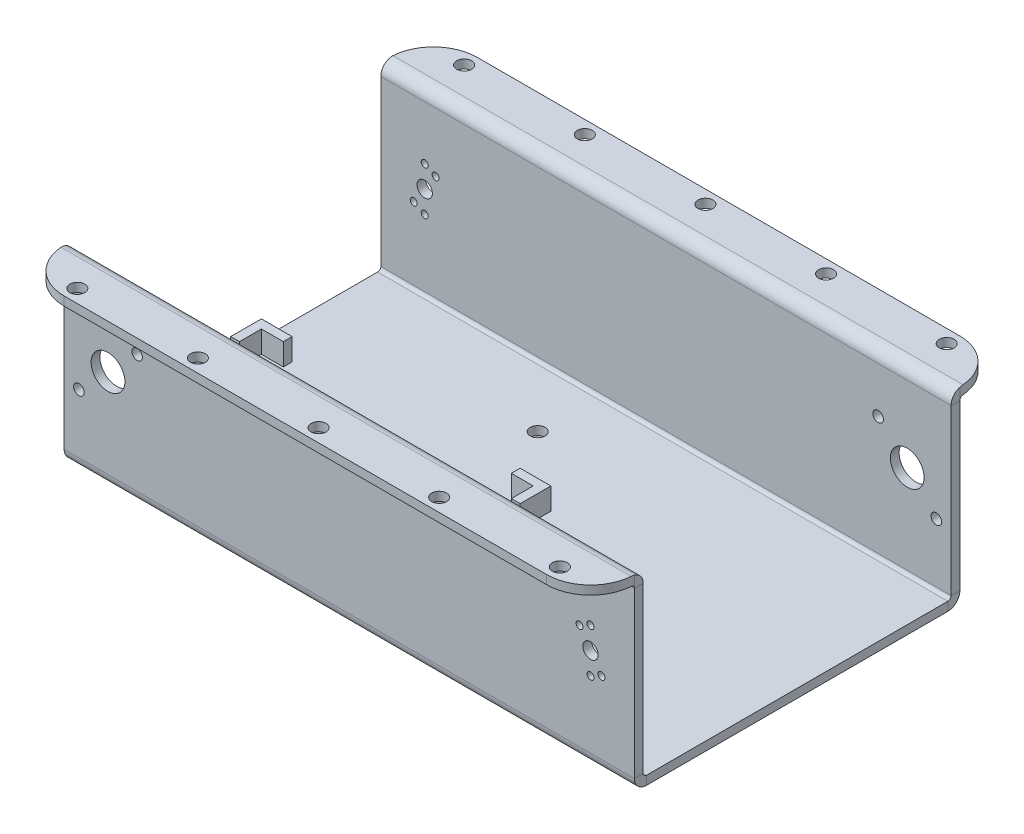
SolidWorks part; units mm, degrees
note: The reader was unsure of these and kept them because the rebuilt part matched: flange length of "边线-法兰1", "边线-法兰2".
material "PE(聚乙烯)"
ref_plane "前视基准面" through (0, 0, 0) normal (0, 0, 1) x (1, 0, 0)
ref_plane "上视基准面" through (0, 0, 0) normal (0, 1, 0) x (1, 0, 0)
ref_plane "右视基准面" through (0, 0, 0) normal (1, 0, 0) x (0, 0, -1)
other "Configuration Table"
sketch "草图1" plane through (0, 0, 0) normal (0, 1, 0) x (1, 0, 0)
  line L1 (-65, 37.1) -> (65, 37.1)
  line L2 (-65, 37.1) -> (-65, -37.1)
  line L3 (-65, -37.1) -> (65, -37.1)
  line L4 (65, 37.1) -> (65, -37.1)
  line L5 (-65, 37.1) -> (65, -37.1) construction
  line L6 (-65, -37.1) -> (65, 37.1) construction
  point P0 (0, 0)
  dimension "D1" = 130
  dimension "D2" = 74.2
base flange "基体-法兰1" sketch "草图1" thickness 2 reverse thickness direction no parameters "D1"=0.7366
edge flange "边线-法兰1" sketch "草图10" flange profiles "草图10", "草图11" flange angle 90 flange length 43 flange position material inside bend radius 0.7366 thickness 2 relief rectangular parameters "D6"=10, "D8"=1
sketch "草图10" plane through (0, 0, 37.1) normal (0, 0, 1) x (1, 0, 0)
  line L0 (-65, 0) -> (65, 0) construction
  line L1 (-65, 0) -> (65, 0)
  line L2 (-65, 0) -> (-65, 41)
  line L3 (-65, 41) -> (65, 41)
  line L4 (65, 41) -> (65, 0)
sketch "草图11" plane through (0, 0, -37.1) normal (0, 0, -1) x (-1, 0, 0)
  line L0 (-65, 0) -> (65, 0) construction
  line L1 (-65, 0) -> (65, 0)
  line L2 (-65, 0) -> (-65, 41)
  line L3 (-65, 41) -> (65, 41)
  line L4 (65, 41) -> (65, 0)
bend "边线折弯1" bend radius 0.7366 bend angle 90 parameters "D5"=1
bend "边线折弯2" bend radius 0.7366 bend angle 90 parameters "D5"=2
edge flange "边线-法兰2" sketch "草图16" flange profiles "草图16", "草图17" flange angle 90 flange length 12 flange position material inside bend radius 0.7366 thickness 2 relief rectangular parameters "D6"=10, "D8"=1
sketch "草图16" plane through (0, 41, 37.1) normal (0, 1, 0) x (-1, 0, 0)
  line L0 (-65, 0) -> (65, 0) construction
  line L1 (-65, 0) -> (65, 0)
  line L2 (-65, 0) -> (-65, 10)
  line L3 (-65, 10) -> (65, 10)
  line L4 (65, 10) -> (65, 0)
sketch "草图17" plane through (0, 41, -37.1) normal (0, 1, 0) x (1, 0, 0)
  line L0 (-65, 0) -> (65, 0) construction
  line L1 (-65, 0) -> (65, 0)
  line L2 (-65, 0) -> (-65, 10)
  line L3 (-65, 10) -> (65, 10)
  line L4 (65, 10) -> (65, 0)
bend "边线折弯3" bend radius 0.7366 bend angle 90 parameters "D5"=3
bend "边线折弯4" bend radius 0.7366 bend angle 90 parameters "D5"=4
sketch "草图24" plane through (0, 0, -37.1) normal (0, 0, -1) x (-1, 0, 0)
  line L0 (57.3827, 5.414) -> (62.1487, 5.414) construction
  line L1 (62.1487, 5.414) -> (62.1487, 5.819) construction
  line L2 (62.1487, 5.819) -> (57.3827, 5.819) construction
  line L3 (57.3827, 5.819) -> (57.3827, 5.414) construction
  line L4 (57.3827, 5.414) -> (62.1487, 5.414) construction
  line L5 (62.1487, 5.414) -> (62.1487, 5.819) construction
  line L6 (62.1487, 5.819) -> (57.3827, 5.819) construction
  line L7 (57.3827, 5.819) -> (57.3827, 5.414) construction
  line L8 (57.3827, 5.6165) -> (62.1487, 5.6165) construction
  line L9 (59.7657, 5.819) -> (59.7657, 5.414) construction
  arc A1 (53.882, 22) -> (56.118, 22) centre (55, 21) ccw construction
  circle A2 centre (55, 16) radius 0.625 construction
  circle A3 centre (57.5, 17.25) radius 0.8 construction
  circle A4 centre (52.5, 24.75) radius 0.8 construction
  circle A5 centre (55, 26) radius 0.625 construction
  circle A6 centre (-55, 21) radius 2 construction
  arc A7 (53.882, 22) -> (56.118, 22) centre (55, 21) ccw construction
  circle A8 centre (55, 16) radius 0.625 construction
  circle A9 centre (57.5, 17.25) radius 0.8 construction
  circle A10 centre (52.5, 24.75) radius 0.8 construction
  circle A11 centre (55, 26) radius 0.625 construction
  circle A12 centre (59.7657, 5.6165) radius 1
  circle A18 centre (62.2657, 5.6165) radius 1
  circle A37 centre (41.0157, 3.4515) radius 1
  circle A38 centre (28.5157, 20.772) radius 1
  circle A39 centre (37.2657, 40.2575) radius 1
  circle A40 centre (58.5157, 42.4226) radius 1
  circle A41 centre (71.0157, 25.1021) radius 1
  point P29 (59.7657, 5.6165)
  point P40 (39.7657, 5.6165)
  point P41 (39.7657, 5.6165)
  point P46 (49.7657, 22.937)
  point P65 (39.7657, 5.6165)
  dimension "D1" = 2
  dimension "D3" = 2
  dimension "D2" = 2.5
  dimension "D4" = 6
sketch "草图25" plane through (0, 0, 37.1) normal (0, 0, 1) x (1, 0, 0)
  arc A1 (53.882, 22) -> (56.118, 22) centre (55, 21) ccw construction
  circle A2 centre (55, 16) radius 0.625 construction
  circle A3 centre (57.5, 17.25) radius 0.8 construction
  circle A4 centre (52.5, 24.75) radius 0.8 construction
  circle A5 centre (55, 26) radius 0.625 construction
  circle A6 centre (-55, 21) radius 2
  arc A7 (53.882, 22) -> (56.118, 22) centre (55, 21) ccw
  circle A8 centre (55, 16) radius 0.625
  circle A9 centre (57.5, 17.25) radius 0.8
  circle A10 centre (52.5, 24.75) radius 0.8
  circle A11 centre (55, 26) radius 0.625
hole_wizard "M1.4 间隙孔1" positions "草图27" profile "草图28" hole size "M1.4" standard "GB" end condition up to next
sketch "草图27" plane through (0, 0, -37.1) normal (0, 0, -1) x (-1, 0, 0)
  point P0 (52.5, 24.75)
  point P3 (55, 26)
  point P6 (57.5, 17.25)
  point P9 (55, 16)
sketch "草图28" plane through (-52.5, 24.75, -37.1) normal (1, 0, 0) x (0, 1, 0)
  line L0 (0, 0) -> (0, 2)
  line L1 (0, 2) -> (0.8, 2)
  line L2 (0.8, 2) -> (0.8, 0)
  line L5 (0.8, 0) -> (0, 0)
  line L11 (0, -6.35) -> (0, 107.95) construction
  dimension "通孔孔直径" = 1.6
  dimension "通孔孔深度" = 2
hole_wizard "M1.4 间隙孔2" positions "草图29" profile "草图30" hole size "M1.4" standard "GB" end condition up to next
sketch "草图29" plane through (0, 0, 37.1) normal (0, 0, 1) x (1, 0, 0)
  point P0 (52.5, 24.75)
  point P3 (55, 26)
  point P6 (57.5, 17.25)
  point P9 (55, 16)
sketch "草图30" plane through (52.5, 24.75, 37.1) normal (1, 0, 0) x (0, -1, 0)
  line L0 (0, 0) -> (0, 2)
  line L1 (0, 2) -> (0.8, 2)
  line L2 (0.8, 2) -> (0.8, 0)
  line L5 (0.8, 0) -> (0, 0)
  line L11 (0, -6.35) -> (0, 107.95) construction
  dimension "通孔孔直径" = 1.6
  dimension "通孔孔深度" = 2
hole_wizard "Ø3.5 (3.5) 直径孔1" positions "草图31" profile "草图32" hole size "Ø3.5" standard "GB" end condition up to next
sketch "草图31" plane through (0, 0, -37.1) normal (0, 0, -1) x (-1, 0, 0)
  point P0 (55, 21)
sketch "草图32" plane through (-55, 21, -37.1) normal (1, 0, 0) x (0, 1, 0)
  line L0 (0, 0) -> (0, 2)
  line L1 (0, 2) -> (1.75, 2)
  line L2 (1.75, 2) -> (1.75, 0)
  line L5 (1.75, 0) -> (0, 0)
  line L11 (0, -6.35) -> (0, 107.95) construction
  dimension "通孔孔直径" = 3.5
  dimension "通孔孔深度" = 2
hole_wizard "Ø3.5 (3.5) 直径孔2" positions "草图33" profile "草图34" hole size "Ø3.5" standard "GB" end condition up to next
sketch "草图33" plane through (0, 0, 37.1) normal (0, 0, 1) x (1, 0, 0)
  point P0 (55, 21)
sketch "草图34" plane through (55, 21, 37.1) normal (1, 0, 0) x (0, -1, 0)
  line L0 (0, 0) -> (0, 2)
  line L1 (0, 2) -> (1.75, 2)
  line L2 (1.75, 2) -> (1.75, 0)
  line L5 (1.75, 0) -> (0, 0)
  line L11 (0, -6.35) -> (0, 107.95) construction
  dimension "通孔孔直径" = 3.5
  dimension "通孔孔深度" = 2
hole_wizard "Ø7.7 (7.7) 直径孔1" positions "草图35" profile "草图36" hole size "Ø7.7" standard "GB" end condition up to next
sketch "草图35" plane through (0, 0, -37.1) normal (0, 0, -1) x (-1, 0, 0)
  point P0 (-55, 21)
sketch "草图36" plane through (55, 21, -37.1) normal (1, 0, 0) x (0, 1, 0)
  line L0 (0, 0) -> (0, 2)
  line L1 (0, 2) -> (3.85, 2)
  line L2 (3.85, 2) -> (3.85, 0)
  line L5 (3.85, 0) -> (0, 0)
  line L11 (0, -6.35) -> (0, 107.95) construction
  dimension "通孔孔直径" = 7.7
  dimension "通孔孔深度" = 2
hole_wizard "Ø7.7 (7.7) 直径孔2" positions "草图37" profile "草图38" hole size "Ø7.7" standard "GB" end condition up to next
sketch "草图37" plane through (0, 0, 37.1) normal (0, 0, 1) x (1, 0, 0)
  point P0 (-55, 21)
sketch "草图38" plane through (-55, 21, 37.1) normal (1, 0, 0) x (0, -1, 0)
  line L0 (0, 0) -> (0, 2)
  line L1 (0, 2) -> (3.85, 2)
  line L2 (3.85, 2) -> (3.85, 0)
  line L5 (3.85, 0) -> (0, 0)
  line L11 (0, -6.35) -> (0, 107.95) construction
  dimension "通孔孔直径" = 7.7
  dimension "通孔孔深度" = 2
sketch "草图43" plane through (0, 41, 0) normal (0, 1, 0) x (1, 0, 0)
  line L0 (65, 47.1) -> (-65, 47.1) construction
  line L1 (-55, -44.1) -> (55, -44.1) construction
  line L2 (-55, -44.1) -> (-55, 44.1) construction
  line L3 (-55, 44.1) -> (55, 44.1) construction
  line L4 (55, -44.1) -> (55, 44.1) construction
  line L5 (-55, -44.1) -> (55, 44.1) construction
  line L6 (-55, 44.1) -> (55, -44.1) construction
  line L8 (65, 37.8366) -> (65, 47.1) construction
  line L9 (0, 44.1) -> (0, -44.1) construction
  line L10 (-27.5, 44.1) -> (-27.5, -44.1) construction
  line L11 (27.5, 44.1) -> (27.5, -44.1) construction
  point P0 (0, 0)
  dimension "D1" = 3
  dimension "D2" = 10
  dimension "D3" = 27.5
hole_wizard "M3 间隙孔2" positions "草图44" profile "草图45" hole size "M3" standard "GB" end condition through all
sketch "草图44" plane through (0, 41, 0) normal (0, 1, 0) x (1, 0, 0)
  line L0 (-55, 44.1) -> (55, 44.1) construction
  point P0 (-55, 44.1)
  point P3 (-27.5, 44.1)
  point P6 (27.5, 44.1)
  point P9 (55, 44.1)
  point P12 (55, -44.1)
  point P15 (27.5, -44.1)
  point P18 (0, -44.1)
  point P21 (-27.5, -44.1)
  point P24 (-55, -44.1)
  point P27 (0, 44.1)
sketch "草图45" plane through (-55, 41, -44.1) normal (1, 0, 0) x (0, 0, 1)
  line L0 (0, 0) -> (0, 43)
  line L1 (0, 43) -> (1.7, 43)
  line L2 (1.7, 43) -> (1.7, 0)
  line L5 (1.7, 0) -> (0, 0)
  line L11 (0, -6.35) -> (0, 107.95) construction
  dimension "通孔孔直径" = 3.4
  dimension "通孔孔深度" = 43
sketch "草图46" plane through (0, 0, 0) normal (0, 1, 0) x (1, 0, 0)
  line L2 (1.9747, 6.87) -> (-5.0253, 6.87)
  line L3 (-64, 6.87) -> (-64, -0.13)
  line L17 (-0.0253, -32.8747) -> (-0.0253, 7.1) construction
  line L18 (-0.0253, 4.87) -> (-62, 4.87) construction
  line L19 (-62, 7.1) -> (-62, -32.8747) construction
  line L24 (-57, 6.87) -> (-57, 4.87)
  line L25 (-64, -0.13) -> (-62, -0.13)
  line L27 (-5.0253, 6.87) -> (-5.0253, 4.87)
  line L28 (-62, 4.87) -> (-57, 4.87)
  line L29 (-62, 4.87) -> (-62, -0.13)
  line L31 (-0.0253, -0.13) -> (1.9747, -0.13)
  line L36 (-0.0253, 4.87) -> (-0.0253, -0.13)
  line L37 (-0.0253, 4.87) -> (-5.0253, 4.87)
  line L40 (-57, 6.87) -> (-64, 6.87)
  line L43 (1.9747, -0.13) -> (1.9747, 6.87)
  dimension "D3" = 5
  dimension "D4" = 5
  dimension "D6" = 5
extrude "凸台-拉伸1" add sketch "草图46" along normal blind 5
sketch "草图67" plane through (0, 0, 35.1) normal (0, 0, -1) x (-1, 0, 0)
  circle A4 centre (48.3667, 27.8007) radius 1.2
  circle A5 centre (61.6333, 14.1993) radius 1.2
  circle A6 centre (-48.3667, 27.8007) radius 1.2
  circle A7 centre (-61.6333, 14.1993) radius 1.2
hole_wizard "M2 间隙孔4" positions "草图70" profile "草图71" hole size "M2" standard "GB" end condition up to next
sketch "草图70" plane through (0, 0, -37.1) normal (0, 0, -1) x (-1, 0, 0)
  point P0 (-48.3667, 27.8007)
  point P3 (-61.6333, 14.1993)
sketch "草图71" plane through (48.3667, 27.8007, -37.1) normal (1, 0, 0) x (0, 1, 0)
  line L0 (0, 0) -> (0, 2)
  line L1 (0, 2) -> (1.2, 2)
  line L2 (1.2, 2) -> (1.2, 0)
  line L5 (1.2, 0) -> (0, 0)
  line L11 (0, -6.35) -> (0, 107.95) construction
  dimension "通孔孔直径" = 2.4
  dimension "通孔孔深度" = 2
hole_wizard "M2 间隙孔5" positions "草图72" profile "草图73" hole size "M2" standard "GB" end condition up to next
sketch "草图72" plane through (0, 0, 35.1) normal (0, 0, -1) x (-1, 0, 0)
  point P0 (48.3667, 27.8007)
  point P3 (61.6333, 14.1993)
sketch "草图73" plane through (-48.3667, 27.8007, 35.1) normal (1, 0, 0) x (0, 1, 0)
  line L0 (0, 0) -> (0, 2)
  line L1 (0, 2) -> (1.2, 2)
  line L2 (1.2, 2) -> (1.2, 0)
  line L5 (1.2, 0) -> (0, 0)
  line L11 (0, -6.35) -> (0, 107.95) construction
  dimension "通孔孔直径" = 2.4
  dimension "通孔孔深度" = 2
hole_wizard "M3 间隙孔3" positions "草图74" profile "草图75" hole size "M3" standard "GB"
sketch "草图74" plane through (0, 0, 0) normal (0, 1, 0) x (1, 0, 0)
  line L0 (65, 35.1) -> (-65, 35.1) construction
  line L1 (-65, 34.3634) -> (-65, -34.3634) construction
  point P0 (-15.23, 21.09)
  dimension "D1" = 14.01
  dimension "D2" = 49.77
sketch "草图75" plane through (-15.23, 0, -21.09) normal (1, 0, 0) x (0, 0, 1)
  line L0 (0, 0) -> (0, 3)
  line L1 (0, 3) -> (1.7, 1.9785)
  line L2 (1.7, 1.9785) -> (1.7, 0)
  line L5 (1.7, 0) -> (0, 0)
  line L10 (0, 3) -> (-1.7, 1.9785) construction
  line L11 (0, -6.35) -> (0, 107.95) construction
  dimension "孔直径" = 3.4
  dimension "孔深度" = 3
  dimension "导头角度" = 118
fillet "圆角1" radius 10 4 edges at (65, 40, -47.1) (65, 40, 47.1) (-65, 40, 47.1) (-65, 40, -47.1)
sketch "草图78" plane through (0, 41, 0) normal (0, 1, 0) x (1, 0, 0)
  line L0 (-55, -47.1) -> (55, -47.1) construction
  arc A0 (-64.9728, -37.8366) -> (-52.5452, -47.1) centre (-51.6691, -32.9566) ccw
sketch "折弯-线1" [suppressed] plane through (0, 0, 0) normal (0, 1, 0) x (1, 0, 0)
sketch "边界框1" [suppressed] plane through (0, 0, 0) normal (0, 1, 0) x (1, 0, 0)
sheet metal parameters "钣金6" thickness 2 parameters "D1"=0.7366
flat pattern "平板型式6" [suppressed]
sketch "折弯-线2" plane through (0, 0, 0) normal (0, 1, 0) x (1, 0, 0)
sketch "边界框2" [suppressed] plane through (0, 0, 0) normal (0, 1, 0) x (1, 0, 0)
sheet metal parameters "钣金7" thickness 2 parameters "D1"=0.7366
flat pattern "平板型式6" [suppressed]
sketch "折弯-线2" plane through (0, 0, 0) normal (0, 1, 0) x (1, 0, 0)
sketch "边界框2" [suppressed] plane through (0, 0, 0) normal (0, 1, 0) x (1, 0, 0)
bend of the flat pattern "展平-<边线折弯1>1"
bend of the flat pattern "展平-<边线折弯2>1"
sheet metal parameters "钣金8" thickness 2 parameters "D1"=0.7366
flat pattern "平板型式6" [suppressed]
sketch "折弯-线2" plane through (0, 0, 0) normal (0, 1, 0) x (1, 0, 0)
sketch "边界框2" [suppressed] plane through (0, 0, 0) normal (0, 1, 0) x (1, 0, 0)
bend of the flat pattern "展平-<边线折弯1>1"
bend of the flat pattern "展平-<边线折弯2>1"
bend of the flat pattern "展平-<边线折弯3>1"
bend of the flat pattern "展平-<边线折弯4>1"
sheet metal parameters "钣金12" thickness 2 parameters "D1"=0.7366
flat pattern "平板型式6" [suppressed]
sketch "折弯-线2" plane through (0, 0, 0) normal (0, 1, 0) x (1, 0, 0)
sketch "边界框2" [suppressed] plane through (0, 0, 0) normal (0, 1, 0) x (1, 0, 0)
bend of the flat pattern "展平-<边线折弯1>1"
bend of the flat pattern "展平-<边线折弯2>1"
bend of the flat pattern "展平-<边线折弯3>1"
bend of the flat pattern "展平-<边线折弯4>1"
sheet metal parameters "钣金13" thickness 2 parameters "D1"=0.7366
flat pattern "平板型式6" [suppressed]
sketch "折弯-线2" plane through (0, 0, 0) normal (0, 1, 0) x (1, 0, 0)
sketch "边界框2" [suppressed] plane through (0, 0, 0) normal (0, 1, 0) x (1, 0, 0)
bend of the flat pattern "展平-<边线折弯1>1"
bend of the flat pattern "展平-<边线折弯2>1"
bend of the flat pattern "展平-<边线折弯3>1"
bend of the flat pattern "展平-<边线折弯4>1"
sheet metal parameters "钣金14" thickness 2 parameters "D1"=0.7366
flat pattern "平板型式6" [suppressed]
sketch "折弯-线2" plane through (0, 0, 0) normal (0, 1, 0) x (1, 0, 0)
sketch "边界框2" [suppressed] plane through (0, 0, 0) normal (0, 1, 0) x (1, 0, 0)
bend of the flat pattern "展平-<边线折弯1>1"
bend of the flat pattern "展平-<边线折弯2>1"
bend of the flat pattern "展平-<边线折弯3>1"
bend of the flat pattern "展平-<边线折弯4>1"
sheet metal parameters "钣金15" thickness 2 parameters "D1"=0.7366
flat pattern "平板型式6" [suppressed]
sketch "折弯-线2" plane through (0, 0, 0) normal (0, 1, 0) x (1, 0, 0)
sketch "边界框2" [suppressed] plane through (0, 0, 0) normal (0, 1, 0) x (1, 0, 0)
bend of the flat pattern "展平-<边线折弯1>1"
bend of the flat pattern "展平-<边线折弯2>1"
bend of the flat pattern "展平-<边线折弯3>1"
bend of the flat pattern "展平-<边线折弯4>1"
sheet metal parameters "钣金16" thickness 2 parameters "D1"=0.7366
flat pattern "平板型式6" [suppressed]
sketch "折弯-线2" plane through (0, 0, 0) normal (0, 1, 0) x (1, 0, 0)
sketch "边界框2" [suppressed] plane through (0, 0, 0) normal (0, 1, 0) x (1, 0, 0)
bend of the flat pattern "展平-<边线折弯1>1"
bend of the flat pattern "展平-<边线折弯2>1"
bend of the flat pattern "展平-<边线折弯3>1"
bend of the flat pattern "展平-<边线折弯4>1"
sheet metal parameters "钣金17" thickness 2 parameters "D1"=0.7366
flat pattern "平板型式6" [suppressed]
sketch "折弯-线2" plane through (0, 0, 0) normal (0, 1, 0) x (1, 0, 0)
sketch "边界框2" [suppressed] plane through (0, 0, 0) normal (0, 1, 0) x (1, 0, 0)
bend of the flat pattern "展平-<边线折弯1>1"
bend of the flat pattern "展平-<边线折弯2>1"
bend of the flat pattern "展平-<边线折弯3>1"
bend of the flat pattern "展平-<边线折弯4>1"
sheet metal parameters "钣金21" thickness 2 parameters "D1"=0.7366
flat pattern "平板型式6" [suppressed]
sketch "折弯-线2" plane through (0, 0, 0) normal (0, 1, 0) x (1, 0, 0)
  line L0 (65, 72.982) -> (-65, 72.982) construction
  line L1 (-65, -72.982) -> (65, -72.982) construction
  line L2 (65, 35.7273) -> (-65, 35.7273) construction
  line L3 (-65, -35.7273) -> (65, -35.7273) construction
  line L4 (65, 72.982) -> (-65, 72.982) construction
  line L5 (-65, -72.982) -> (65, -72.982) construction
  line L6 (65, 35.7273) -> (-65, 35.7273) construction
  line L7 (-65, -35.7273) -> (65, -35.7273) construction
sketch3d "边界框2" [suppressed]
  line L0 (65, 83.6093, 0) -> (65, -83.6093, 0) construction
  line L1 (-65, 83.6093, 0) -> (-65, -83.6093, 0) construction
  line L2 (65, 83.6093, 0) -> (-65, 83.6093, 0) construction
  line L3 (65, -83.6093, 0) -> (-65, -83.6093, 0) construction
bend of the flat pattern "展平-<边线折弯1>1"
bend of the flat pattern "展平-<边线折弯2>1"
bend of the flat pattern "展平-<边线折弯3>1"
bend of the flat pattern "展平-<边线折弯4>1"
sketch "草图25-1" plane through (0, -2, 36.3546) normal (0, -1, 0) x (1, 0, 0)
  circle A6 centre (-55, 21) radius 2
  arc A7 (53.882, 22) -> (56.118, 22) centre (55, 21) ccw
  circle A8 centre (55, 16) radius 0.625
  circle A9 centre (57.5, 17.25) radius 0.8
  circle A10 centre (52.5, 24.75) radius 0.8
  circle A11 centre (55, 26) radius 0.625
sketch "草图26-1" plane through (0, -2, 36.3546) normal (0, -1, 0) x (1, 0, 0)
  circle A3 centre (35, 23.5) radius 1.45
  circle A4 centre (0, 23.5) radius 1.45
  circle A5 centre (-35, 23.5) radius 1.45
sketch "草图43-1" plane through (0, 0, -36.5093) normal (0, 1, 0) x (1, 0, 0)
  line L0 (62, 47.1) -> (-62, 47.1) construction
  line L1 (-55, -44.1) -> (55, -44.1) construction
  line L2 (-55, -44.1) -> (-55, 44.1) construction
  line L3 (-55, 44.1) -> (55, 44.1) construction
  line L4 (55, -44.1) -> (55, 44.1) construction
  line L5 (-55, -44.1) -> (55, 44.1) construction
  line L6 (-55, 44.1) -> (55, -44.1) construction
  line L8 (65, -117.1186) -> (65, 44.1) construction
  line L9 (0, 44.1) -> (0, -44.1) construction
  line L10 (-27.5, 44.1) -> (-27.5, -44.1) construction
  line L11 (27.5, 44.1) -> (27.5, -44.1) construction
  point P0 (0, 0)
  dimension "D1" = 3
  dimension "D2" = 10
  dimension "D3" = 27.5
sheet metal parameters "钣金22" thickness 2 parameters "D1"=0.7366
flat pattern "平板型式6" [suppressed]
sketch "折弯-线2" plane through (0, 0, 0) normal (0, 1, 0) x (1, 0, 0)
  line L0 (65, 72.982) -> (-65, 72.982) construction
  line L1 (-65, -72.982) -> (65, -72.982) construction
  line L2 (65, 35.7273) -> (-65, 35.7273) construction
  line L3 (-65, -35.7273) -> (65, -35.7273) construction
  line L4 (65, 72.982) -> (-65, 72.982) construction
  line L5 (-65, -72.982) -> (65, -72.982) construction
  line L6 (65, 35.7273) -> (-65, 35.7273) construction
  line L7 (-65, -35.7273) -> (65, -35.7273) construction
sketch3d "边界框2" [suppressed]
  line L0 (65, 83.6093, 0) -> (65, -83.6093, 0) construction
  line L1 (-65, 83.6093, 0) -> (-65, -83.6093, 0) construction
  line L2 (65, 83.6093, 0) -> (-65, 83.6093, 0) construction
  line L3 (65, -83.6093, 0) -> (-65, -83.6093, 0) construction
bend of the flat pattern "展平-<边线折弯1>1"
bend of the flat pattern "展平-<边线折弯2>1"
bend of the flat pattern "展平-<边线折弯3>1"
bend of the flat pattern "展平-<边线折弯4>1"
sketch "草图25-1" plane through (0, -2, 36.3546) normal (0, -1, 0) x (1, 0, 0)
  circle A6 centre (-55, 21) radius 2
  arc A7 (53.882, 22) -> (56.118, 22) centre (55, 21) ccw
  circle A8 centre (55, 16) radius 0.625
  circle A9 centre (57.5, 17.25) radius 0.8
  circle A10 centre (52.5, 24.75) radius 0.8
  circle A11 centre (55, 26) radius 0.625
sketch "草图26-1" plane through (0, -2, 36.3546) normal (0, -1, 0) x (1, 0, 0)
  circle A3 centre (35, 23.5) radius 1.45
  circle A4 centre (0, 23.5) radius 1.45
  circle A5 centre (-35, 23.5) radius 1.45
sketch "草图43-1" plane through (0, 0, -36.5093) normal (0, 1, 0) x (1, 0, 0)
  line L0 (62, 47.1) -> (-62, 47.1)
  line L1 (-55, -44.1) -> (55, -44.1) construction
  line L2 (-55, -44.1) -> (-55, 44.1) construction
  line L3 (-55, 44.1) -> (55, 44.1) construction
  line L4 (55, -44.1) -> (55, 44.1) construction
  line L5 (-55, -44.1) -> (55, 44.1) construction
  line L6 (-55, 44.1) -> (55, -44.1) construction
  line L8 (65, -117.1186) -> (65, 44.1)
  line L9 (0, 44.1) -> (0, -44.1) construction
  line L10 (-27.5, 44.1) -> (-27.5, -44.1) construction
  line L11 (27.5, 44.1) -> (27.5, -44.1) construction
  point P0 (0, 0)
  dimension "D1" = 3
  dimension "D2" = 10
  dimension "D3" = 27.5
sheet metal parameters "钣金31" thickness 2 parameters "D1"=0.7366
flat pattern "平板型式6" [suppressed]
sketch "折弯-线2" plane through (0, 0, 0) normal (0, 1, 0) x (1, 0, 0)
  line L0 (65, 72.982) -> (-65, 72.982) construction
  line L1 (-65, -72.982) -> (65, -72.982) construction
  line L2 (65, 35.7273) -> (-65, 35.7273) construction
  line L3 (-65, -35.7273) -> (65, -35.7273) construction
  line L4 (65, 72.982) -> (-65, 72.982) construction
  line L5 (-65, -72.982) -> (65, -72.982) construction
  line L6 (65, 35.7273) -> (-65, 35.7273) construction
  line L7 (-65, -35.7273) -> (65, -35.7273) construction
sketch3d "边界框2" [suppressed]
  line L0 (65, 83.6093, 0) -> (65, -83.6093, 0) construction
  line L1 (-65, 83.6093, 0) -> (-65, -83.6093, 0) construction
  line L2 (65, 83.6093, 0) -> (-65, 83.6093, 0) construction
  line L3 (65, -83.6093, 0) -> (-65, -83.6093, 0) construction
bend of the flat pattern "展平-<边线折弯1>1"
bend of the flat pattern "展平-<边线折弯2>1"
bend of the flat pattern "展平-<边线折弯3>1"
bend of the flat pattern "展平-<边线折弯4>1"
sketch "草图25-1" plane through (0, -2, 36.3546) normal (0, -1, 0) x (1, 0, 0)
  circle A6 centre (-55, 21) radius 2
  arc A7 (53.882, 22) -> (56.118, 22) centre (55, 21) ccw
  circle A8 centre (55, 16) radius 0.625
  circle A9 centre (57.5, 17.25) radius 0.8
  circle A10 centre (52.5, 24.75) radius 0.8
  circle A11 centre (55, 26) radius 0.625
sketch "草图26-1" plane through (0, -2, 36.3546) normal (0, -1, 0) x (1, 0, 0)
  circle A3 centre (35, 23.5) radius 1.45
  circle A4 centre (0, 23.5) radius 1.45
  circle A5 centre (-35, 23.5) radius 1.45
sketch "草图43-1" plane through (0, 0, -36.5093) normal (0, 1, 0) x (1, 0, 0)
  line L0 (62, 47.1) -> (-62, 47.1)
  line L1 (-55, -44.1) -> (55, -44.1) construction
  line L2 (-55, -44.1) -> (-55, 44.1) construction
  line L3 (-55, 44.1) -> (55, 44.1) construction
  line L4 (55, -44.1) -> (55, 44.1) construction
  line L5 (-55, -44.1) -> (55, 44.1) construction
  line L6 (-55, 44.1) -> (55, -44.1) construction
  line L8 (65, -117.1186) -> (65, 44.1)
  line L9 (0, 44.1) -> (0, -44.1) construction
  line L10 (-27.5, 44.1) -> (-27.5, -44.1) construction
  line L11 (27.5, 44.1) -> (27.5, -44.1) construction
  point P0 (0, 0)
  dimension "D1" = 3
  dimension "D2" = 10
  dimension "D3" = 27.5
sheet metal parameters "钣金32" thickness 2 parameters "D1"=0.7366
flat pattern "平板型式6" [suppressed]
sketch "折弯-线2" plane through (0, 0, 0) normal (0, 1, 0) x (1, 0, 0)
  line L0 (65, 72.982) -> (-65, 72.982) construction
  line L1 (-65, -72.982) -> (65, -72.982) construction
  line L2 (65, 35.7273) -> (-65, 35.7273) construction
  line L3 (-65, -35.7273) -> (65, -35.7273) construction
  line L4 (65, 72.982) -> (-65, 72.982) construction
  line L5 (-65, -72.982) -> (65, -72.982) construction
  line L6 (65, 35.7273) -> (-65, 35.7273) construction
  line L7 (-65, -35.7273) -> (65, -35.7273) construction
sketch3d "边界框2" [suppressed]
  line L0 (65, 83.6093, 0) -> (65, -83.6093, 0) construction
  line L1 (-65, 83.6093, 0) -> (-65, -83.6093, 0) construction
  line L2 (65, 83.6093, 0) -> (-65, 83.6093, 0) construction
  line L3 (65, -83.6093, 0) -> (-65, -83.6093, 0) construction
bend of the flat pattern "展平-<边线折弯1>1"
bend of the flat pattern "展平-<边线折弯2>1"
bend of the flat pattern "展平-<边线折弯3>1"
bend of the flat pattern "展平-<边线折弯4>1"
sketch "草图25-1" plane through (0, -2, 36.3546) normal (0, -1, 0) x (1, 0, 0)
  circle A6 centre (-55, 21) radius 2
  arc A7 (53.882, 22) -> (56.118, 22) centre (55, 21) ccw
  circle A8 centre (55, 16) radius 0.625
  circle A9 centre (57.5, 17.25) radius 0.8
  circle A10 centre (52.5, 24.75) radius 0.8
  circle A11 centre (55, 26) radius 0.625
sketch "草图26-1" plane through (0, -2, 36.3546) normal (0, -1, 0) x (1, 0, 0)
  circle A3 centre (35, 23.5) radius 1.45
  circle A4 centre (0, 23.5) radius 1.45
  circle A5 centre (-35, 23.5) radius 1.45
sketch "草图43-1" plane through (0, 0, -36.5093) normal (0, 1, 0) x (1, 0, 0)
  line L0 (62, 47.1) -> (-62, 47.1)
  line L1 (-55, -44.1) -> (55, -44.1) construction
  line L2 (-55, -44.1) -> (-55, 44.1) construction
  line L3 (-55, 44.1) -> (55, 44.1) construction
  line L4 (55, -44.1) -> (55, 44.1) construction
  line L5 (-55, -44.1) -> (55, 44.1) construction
  line L6 (-55, 44.1) -> (55, -44.1) construction
  line L8 (65, -117.1186) -> (65, 44.1)
  line L9 (0, 44.1) -> (0, -44.1) construction
  line L10 (-27.5, 44.1) -> (-27.5, -44.1) construction
  line L11 (27.5, 44.1) -> (27.5, -44.1) construction
  point P0 (0, 0)
  dimension "D1" = 3
  dimension "D2" = 10
  dimension "D3" = 27.5
sheet metal parameters "钣金33" thickness 2 parameters "D1"=0.7366
flat pattern "平板型式6" [suppressed]
sketch "折弯-线2" plane through (0, 0, 0) normal (0, 1, 0) x (1, 0, 0)
  line L0 (65, 72.982) -> (-65, 72.982) construction
  line L1 (-65, -72.982) -> (65, -72.982) construction
  line L2 (65, 35.7273) -> (-65, 35.7273) construction
  line L3 (-65, -35.7273) -> (65, -35.7273) construction
  line L4 (65, 72.982) -> (-65, 72.982) construction
  line L5 (-65, -72.982) -> (65, -72.982) construction
  line L6 (65, 35.7273) -> (-65, 35.7273) construction
  line L7 (-65, -35.7273) -> (65, -35.7273) construction
sketch3d "边界框2" [suppressed]
  line L0 (65, 83.6093, 0) -> (65, -83.6093, 0) construction
  line L1 (-65, 83.6093, 0) -> (-65, -83.6093, 0) construction
  line L2 (65, 83.6093, 0) -> (-65, 83.6093, 0) construction
  line L3 (65, -83.6093, 0) -> (-65, -83.6093, 0) construction
bend of the flat pattern "展平-<边线折弯1>1"
bend of the flat pattern "展平-<边线折弯2>1"
bend of the flat pattern "展平-<边线折弯3>1"
bend of the flat pattern "展平-<边线折弯4>1"
sketch "草图25-1" plane through (0, -2, 36.3546) normal (0, -1, 0) x (1, 0, 0)
  circle A6 centre (-55, 21) radius 2
  arc A7 (53.882, 22) -> (56.118, 22) centre (55, 21) ccw
  circle A8 centre (55, 16) radius 0.625
  circle A9 centre (57.5, 17.25) radius 0.8
  circle A10 centre (52.5, 24.75) radius 0.8
  circle A11 centre (55, 26) radius 0.625
sketch "草图26-1" plane through (0, -2, 36.3546) normal (0, -1, 0) x (1, 0, 0)
  circle A3 centre (35, 23.5) radius 1.45
  circle A4 centre (0, 23.5) radius 1.45
  circle A5 centre (-35, 23.5) radius 1.45
sketch "草图43-1" plane through (0, 0, -36.5093) normal (0, 1, 0) x (1, 0, 0)
  line L0 (62, 47.1) -> (-62, 47.1)
  line L1 (-55, -44.1) -> (55, -44.1) construction
  line L2 (-55, -44.1) -> (-55, 44.1) construction
  line L3 (-55, 44.1) -> (55, 44.1) construction
  line L4 (55, -44.1) -> (55, 44.1) construction
  line L5 (-55, -44.1) -> (55, 44.1) construction
  line L6 (-55, 44.1) -> (55, -44.1) construction
  line L8 (65, -117.1186) -> (65, 44.1)
  line L9 (0, 44.1) -> (0, -44.1) construction
  line L10 (-27.5, 44.1) -> (-27.5, -44.1) construction
  line L11 (27.5, 44.1) -> (27.5, -44.1) construction
  point P0 (0, 0)
  dimension "D1" = 3
  dimension "D2" = 10
  dimension "D3" = 27.5
